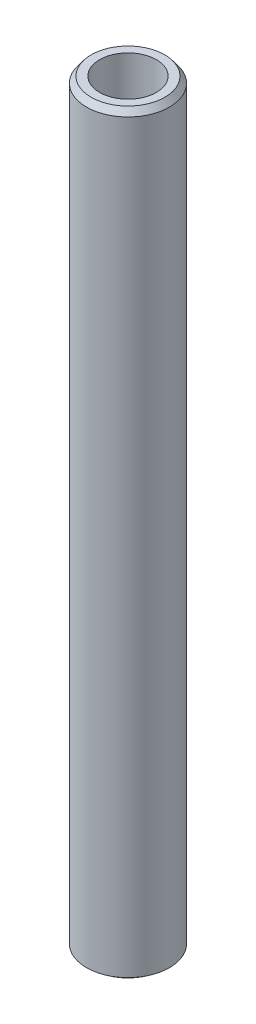
SolidWorks part; units mm, degrees
ref_plane "Front Plane" through (0, 0, 0) normal (0, 0, 1) x (1, 0, 0)
ref_plane "Top Plane" through (0, 0, 0) normal (0, 1, 0) x (1, 0, 0)
ref_plane "Right Plane" through (0, 0, 0) normal (1, 0, 0) x (0, 0, -1)
sketch "Sketch1" plane through (0, 0, 0) normal (0, 1, 0) x (1, 0, 0)
  circle A0 centre (0, 0) radius 15
  dimension "SHAFT_OD" = 30
extrude "Boss-Extrude1" add sketch "Sketch1" along normal blind 273.5343
sketch "Sketch2" plane through (0, 0, 0) normal (0, 1, 0) x (1, 0, 0)
  circle A0 centre (0, 0) radius 10.2729
  dimension "BORE_D" = 20.5458
extrude "Cut-Extrude1" cut sketch "Sketch2" along normal through all
chamfer "Chamfer1" distance 2.232 angle 37.102 2 edges at (0, 273.5343, 15) (0, 0, 15) first distance on face at (0, 273.5343, 15) first distance on face at (0, 0, 10.2729)
